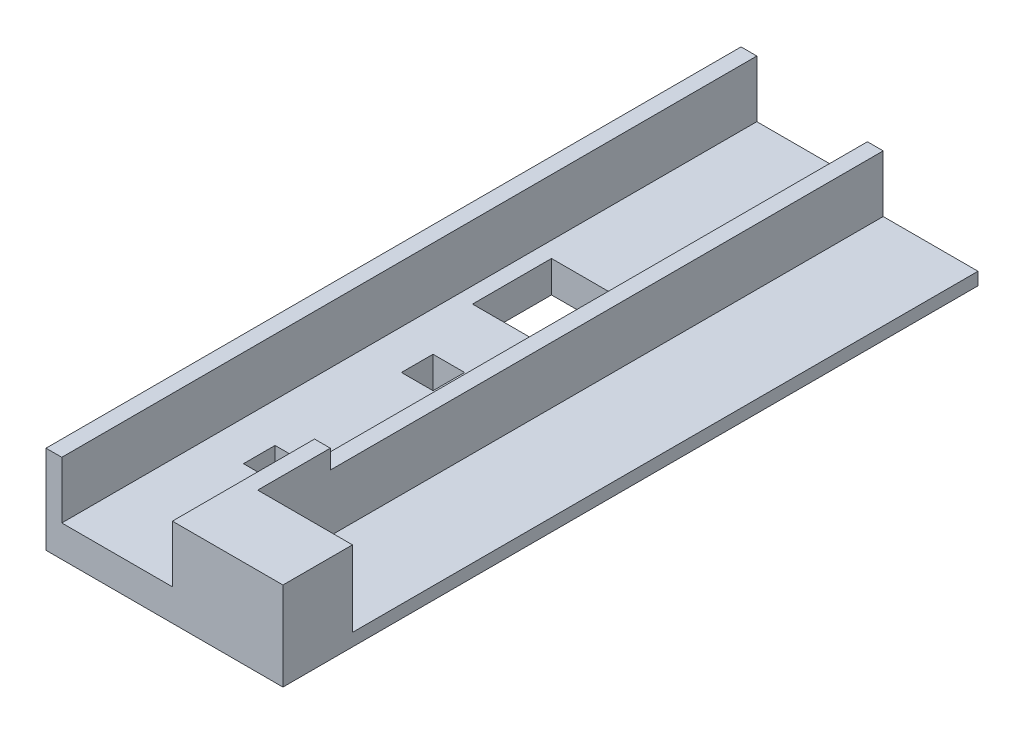
SolidWorks part; units mm, degrees
ref_plane "Płaszczyzna przednia" through (0, 0, 0) normal (0, 0, 1) x (1, 0, 0)
ref_plane "Płaszczyzna górna" through (0, 0, 0) normal (0, 1, 0) x (1, 0, 0)
ref_plane "Płaszczyzna prawa" through (0, 0, 0) normal (1, 0, 0) x (0, 0, -1)
sketch "Szkic1" plane through (0, 0, 0) normal (0, 0, 1) x (1, 0, 0)
  line L0 (0, 0) -> (0, 40.355) construction
  line L2 (17.5, 18) -> (-17.5, 18)
  line L3 (17.5, 18) -> (17.5, 0)
  line L4 (17.5, 0) -> (-17.5, 0)
  line L5 (-17.5, 18) -> (-17.5, 0)
  line L6 (17.5, 18) -> (-17.5, 0) construction
  line L7 (17.5, 0) -> (-17.5, 18) construction
  line L8 (17.5, 18) -> (22.5, 18)
  line L9 (52.5, -6) -> (22.5, -6)
  line L10 (52.5, -6) -> (52.5, 18)
  line L11 (52.5, 18) -> (22.5, 18)
  line L12 (22.5, -6) -> (22.5, 18)
  line L13 (52.5, -6) -> (22.5, 18) construction
  line L14 (52.5, 18) -> (22.5, -6) construction
  line L15 (-17.5, 18) -> (-22.5, 18)
  line L16 (-22.5, 18) -> (-22.5, -10)
  line L17 (-22.5, -10) -> (52.5, -10)
  line L18 (52.5, -10) -> (52.5, -6)
  point P3 (0, 9)
  point P17 (0, 0)
  dimension "D1" = 35
  dimension "D2" = 18
  dimension "D3" = 5
  dimension "D4" = 30
  dimension "D5" = 4
  dimension "D6" = 5
  dimension "D7" = 10
extrude "Dodanie-wyciągnięcie1" add sketch "Szkic1" against normal blind 220 contours L17 L18 L9 L12 L8 L3 L4 L5 L15 L16 region at (6, -2.12, 0)
sketch "Szkic4" plane through (0, 0, 0) normal (0, 0, 1) x (1, 0, 0)
  line L0 (52.5, -10) -> (52.5, -6) construction
  line L1 (22.5, -6) -> (52.5, -6)
  line L2 (22.5, -6) -> (22.5, 18)
  line L3 (22.5, 18) -> (52.5, 18)
  line L4 (52.5, -6) -> (52.5, 18)
  line L5 (17.5, 18) -> (22.5, 18) construction
extrude "Dodanie-wyciągnięcie3" add sketch "Szkic4" against normal blind 5
sketch "Szkic5" plane through (0, 0, 0) normal (0, 1, 0) x (1, 0, 0)
  line L0 (0, 0) -> (0, 220) construction
  line L1 (17.5, 220) -> (-17.5, 220) construction
  line L2 (17.5, 0) -> (-17.5, 0) construction
  line L3 (5, 45) -> (-5, 45)
  line L4 (5, 45) -> (5, 55)
  line L5 (5, 55) -> (-5, 55)
  line L6 (-5, 45) -> (-5, 55)
  line L7 (5, 45) -> (-5, 55) construction
  line L8 (5, 55) -> (-5, 45) construction
  line L10 (5, 105) -> (-5, 105)
  line L11 (5, 105) -> (5, 95)
  line L12 (5, 95) -> (-5, 95)
  line L13 (-5, 105) -> (-5, 95)
  line L14 (5, 105) -> (-5, 95) construction
  line L15 (5, 95) -> (-5, 105) construction
  line L16 (12.5, 150) -> (-12.5, 150)
  line L17 (12.5, 150) -> (12.5, 125)
  line L18 (12.5, 125) -> (-12.5, 125)
  line L19 (-12.5, 150) -> (-12.5, 125)
  line L20 (12.5, 150) -> (-12.5, 125) construction
  line L21 (12.5, 125) -> (-12.5, 150) construction
  point P5 (0, 50)
  point P10 (0, 137.5)
  point P13 (0, 100)
  dimension "D1" = 10
  dimension "D2" = 45
  dimension "D3" = 50
  dimension "D4" = 20
  dimension "D5" = 25
extrude "Wytnij-wyciągnięcie1" cut sketch "Szkic5" against normal blind 25
sketch "Szkic6" plane through (0, 18, 0) normal (0, 1, 0) x (1, 0, 0)
  line L0 (22.5, 220) -> (22.5, 5) construction
  line L1 (17.5, 220) -> (22.5, 220)
  line L2 (17.5, 220) -> (17.5, 45)
  line L3 (17.5, 45) -> (22.5, 45)
  line L4 (22.5, 220) -> (22.5, 45)
  line L5 (17.5, 0) -> (52.5, 0) construction
  dimension "D1" = 45
extrude "Wytnij-wyciągnięcie2" cut sketch "Szkic6" against normal blind 6
sketch "Szkic7" plane through (0, 0, -5) normal (0, 0, -1) x (-1, 0, 0)
  line L0 (-37.5, 18) -> (-37.5, -6) construction
  line L1 (-52.5, 18) -> (-22.5, 18) construction
  line L2 (-52.5, -6) -> (-22.5, -6) construction
  line L3 (-43.2983, 11.7983) -> (-37.5, 17.5966)
  line L4 (-37.5, 17.5966) -> (-31.7017, 11.7983)
  line L5 (-39.5966, 15.5) -> (-35.4034, 15.5)
  line L6 (-37.5, 15.5) -> (-37.5, 14.2) construction
  line L8 (-52.5, 18) -> (-22.5, 18)
  line L9 (-52.5, 18) -> (-52.5, -6)
  line L10 (-52.5, -6) -> (-22.5, -6)
  line L11 (-22.5, 18) -> (-22.5, -6)
  circle A0 centre (-37.5, 6) radius 8.2
  line M7 (-22.5, -6) -> (-22.5, 18)
  line M8 (-22.5, 18) -> (-52.5, 18)
  line M9 (-52.5, 18) -> (-52.5, -6)
  line M10 (-52.5, -6) -> (-22.5, -6)
  dimension "D1" = 16.4
  dimension "D2" = 90
  dimension "D3" = 2.5
extrude "Dodanie-wyciągnięcie4" add sketch "Szkic7" along normal blind 10 contours A0 L3 L4 M10 M7 M8 M9 | L3 L5 L4 region at (37.5, 16.1989, -5) region at (37.5, 17.6158, -5)
sketch "Szkic9" plane through (0, 0, -15) normal (0, 0, -1) x (-1, 0, 0)
  line L1 (-52.5, 18) -> (-22.5, 18)
  line L2 (-52.5, 18) -> (-52.5, -6)
  line L3 (-52.5, -6) -> (-22.5, -6)
  line L4 (-22.5, 18) -> (-22.5, -6)
  circle A0 centre (-37.5, 6) radius 11.25
  dimension "D1" = 22.5
extrude "Dodanie-wyciągnięcie5" add sketch "Szkic9" along normal blind 7
